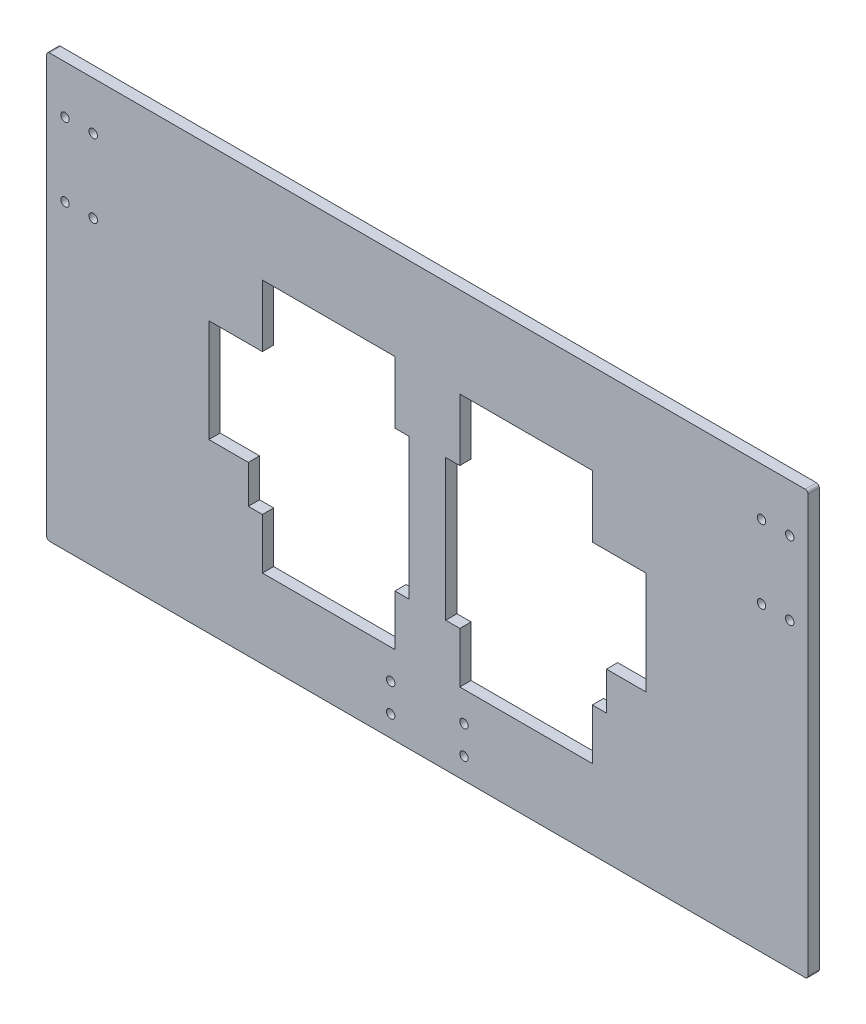
SolidWorks part; units mm, degrees
ref_plane "前视基准面" through (0, 0, 0) normal (0, 0, 1) x (1, 0, 0)
ref_plane "上视基准面" through (0, 0, 0) normal (0, 1, 0) x (1, 0, 0)
ref_plane "右视基准面" through (0, 0, 0) normal (1, 0, 0) x (0, 0, -1)
sketch "草图1" plane through (0, 0, 0) normal (0, 0, 1) x (1, 0, 0)
  line L1 (-135, -75) -> (135, -75)
  line L2 (-135, -75) -> (-135, 75)
  line L3 (-135, 75) -> (135, 75)
  line L4 (135, -75) -> (135, 75)
  line L5 (-135, -75) -> (135, 75) construction
  line L6 (-135, 75) -> (135, -75) construction
  point P0 (0, 0)
  dimension "D1" = 270
  dimension "D2" = 150
base flange "基体-法兰1" sketch "草图1" thickness 4 reverse thickness direction no parameters "D1"=10
fillet "圆角1" radius 1 4 edges at (135, -75, -2) (135, 75, -2) (-135, -75, -2) (-135, 75, -2)
sketch "草图2" plane through (0, 0, -4) normal (0, 0, -1) x (-1, 0, 0)
  line L0 (134, -75) -> (-134, -75) construction
  circle A0 centre (-13, -67.5) radius 1.5
  circle A1 centre (-13, -57.5) radius 1.5
  circle A2 centre (13, -57.5) radius 1.5
  circle A3 centre (13, -67.5) radius 1.5
  point P11 (0, 0)
  point P12 (0, 0)
  dimension "D1" = 3
  dimension "D2" = 3
  dimension "D3" = 3
  dimension "D4" = 3
  dimension "D5" = 13
  dimension "D6" = 13
  dimension "D7" = 13
  dimension "D8" = 13
  dimension "D9" = 7.5
  dimension "D10" = 7.5
  dimension "D11" = 10
  dimension "D12" = 10
extrude "切除-拉伸1" cut sketch "草图2" against normal blind 10 normal cut yes
sketch "草图3" plane through (0, 0, -4) normal (0, 0, -1) x (-1, 0, 0)
  line L0 (-135, -74) -> (-135, 74) construction
  line L1 (134, -75) -> (-134, -75) construction
  circle A0 centre (-128.5, 58) radius 1.5
  circle A1 centre (-128.5, 32) radius 1.5
  circle A2 centre (-118.5, 58) radius 1.5
  circle A3 centre (-118.5, 32) radius 1.5
  dimension "D7" = 3
  dimension "D8" = 3
  dimension "D9" = 3
  dimension "D10" = 3
  dimension "D1" = 6.5
  dimension "D2" = 6.5
  dimension "D3" = 10
  dimension "D4" = 10
  dimension "D5" = 26
  dimension "D6" = 26
  dimension "D11" = 107
extrude "切除-拉伸2" cut sketch "草图3" against normal blind 10 normal cut yes
mirror "镜向1" about plane through (0, 0, 0) normal (1, 0, 0) of "切除-拉伸2"
sketch "草图4" plane through (0, 0, -4) normal (0, 0, -1) x (-1, 0, 0)
  line L0 (134, -75) -> (-134, -75) construction
  line L1 (-58.5, -47) -> (-11.5, -47)
  line L2 (-58.5, -47) -> (-58.5, 43)
  line L3 (-58.5, 43) -> (-11.5, 43)
  line L4 (-11.5, -47) -> (-11.5, 43)
  line L5 (-58.5, -47) -> (-11.5, 43) construction
  line L6 (-58.5, 43) -> (-11.5, -47) construction
  point P0 (-35, -2)
  dimension "D1" = 47
  dimension "D2" = 90
  dimension "D3" = 35
  dimension "D4" = 28
extrude "切除-拉伸3" cut sketch "草图4" against normal blind 10 normal cut yes
sketch "草图5" plane through (0, 0, 0) normal (0, 0, 1) x (1, 0, 0)
  line L0 (11.5, 43) -> (58.5, 43) construction
  line L1 (6.5, -29) -> (63.5, -29)
  line L2 (6.5, -29) -> (6.5, 21)
  line L3 (6.5, 21) -> (63.5, 21)
  line L4 (63.5, -29) -> (63.5, 21)
  line L5 (6.5, -29) -> (63.5, 21) construction
  line L6 (6.5, 21) -> (63.5, -29) construction
  line L7 (58.5, -47) -> (11.5, -47) construction
  line L8 (11.5, -47) -> (11.5, 43) construction
  point P0 (35, -4)
  dimension "D1" = 57
  dimension "D2" = 22
  dimension "D3" = 18
  dimension "D4" = 5
extrude "切除-拉伸4" cut sketch "草图5" against normal blind 10 normal cut yes
sketch "草图6" plane through (0, 0, 0) normal (0, 0, 1) x (1, 0, 0)
  line L0 (58.5, -29) -> (63.5, -29) construction
  line L1 (63.5, 21) -> (77.5, 21)
  line L2 (63.5, 21) -> (63.5, -15.5)
  line L3 (63.5, -15.5) -> (77.5, -15.5)
  line L4 (77.5, 21) -> (77.5, -15.5)
  dimension "D1" = 14
  dimension "D2" = 13.5
extrude "切除-拉伸5" cut sketch "草图6" against normal blind 10 normal cut yes
mirror "镜向2" about plane through (0, 0, 0) normal (1, 0, 0) of "切除-拉伸3", "切除-拉伸4", "切除-拉伸5"
sketch "折弯-线1" [suppressed] plane through (0, 0, 0) normal (0, 1, 0) x (1, 0, 0)
sketch "边界框1" [suppressed] plane through (0, 0, 0) normal (0, 1, 0) x (1, 0, 0)
sheet metal parameters "钣金1" thickness 4 parameters "D1"=10
flat pattern "平板型式1" [suppressed]
sketch "折弯-线2" plane through (0, 0, 0) normal (0, 1, 0) x (1, 0, 0)
sketch3d "边界框2" [suppressed]
  line L0 (-135, -75, 0) -> (135, -75, 0) construction
  line L1 (-135, 75, 0) -> (135, 75, 0) construction
  line L2 (-135, -75, 0) -> (-135, 75, 0) construction
  line L3 (135, -75, 0) -> (135, 75, 0) construction
sheet metal parameters "钣金2" thickness 4 parameters "D1"=10
flat pattern "平板型式1"
sketch "折弯-线2" plane through (0, 0, 0) normal (0, 1, 0) x (1, 0, 0)
sketch3d "边界框2" [suppressed]
  line L0 (-135, -75, 0) -> (135, -75, 0) construction
  line L1 (-135, 75, 0) -> (135, 75, 0) construction
  line L2 (-135, -75, 0) -> (-135, 75, 0) construction
  line L3 (135, -75, 0) -> (135, 75, 0) construction
sheet metal parameters "钣金3" thickness 4 parameters "D1"=10
flat pattern "平板型式1"
sketch "折弯-线2" plane through (0, 0, 0) normal (0, 1, 0) x (1, 0, 0)
sketch3d "边界框2" [suppressed]
  line L0 (-135, -75, 0) -> (135, -75, 0) construction
  line L1 (-135, 75, 0) -> (135, 75, 0) construction
  line L2 (-135, -75, 0) -> (-135, 75, 0) construction
  line L3 (135, -75, 0) -> (135, 75, 0) construction
sheet metal parameters "钣金4" thickness 4 parameters "D1"=10
flat pattern "平板型式1"
sketch "折弯-线2" plane through (0, 0, 0) normal (0, 1, 0) x (1, 0, 0)
sketch3d "边界框2" [suppressed]
  line L0 (-135, -75, 0) -> (135, -75, 0) construction
  line L1 (-135, 75, 0) -> (135, 75, 0) construction
  line L2 (-135, -75, 0) -> (-135, 75, 0) construction
  line L3 (135, -75, 0) -> (135, 75, 0) construction
sheet metal parameters "钣金5" thickness 4 parameters "D1"=10
flat pattern "平板型式1"
sketch "折弯-线2" plane through (0, 0, 0) normal (0, 1, 0) x (1, 0, 0)
sketch3d "边界框2" [suppressed]
  line L0 (-135, -75, 0) -> (135, -75, 0) construction
  line L1 (-135, 75, 0) -> (135, 75, 0) construction
  line L2 (-135, -75, 0) -> (-135, 75, 0) construction
  line L3 (135, -75, 0) -> (135, 75, 0) construction
sheet metal parameters "钣金6" thickness 4 parameters "D1"=10
flat pattern "平板型式1"
sketch "折弯-线2" plane through (0, 0, 0) normal (0, 1, 0) x (1, 0, 0)
sketch3d "边界框2" [suppressed]
  line L0 (-135, -75, 0) -> (135, -75, 0) construction
  line L1 (-135, 75, 0) -> (135, 75, 0) construction
  line L2 (-135, -75, 0) -> (-135, 75, 0) construction
  line L3 (135, -75, 0) -> (135, 75, 0) construction
sheet metal parameters "钣金7" thickness 4 parameters "D1"=10
flat pattern "平板型式1"
sketch "折弯-线2" plane through (0, 0, 0) normal (0, 1, 0) x (1, 0, 0)
sketch3d "边界框2" [suppressed]
  line L0 (-135, -75, 0) -> (135, -75, 0) construction
  line L1 (-135, 75, 0) -> (135, 75, 0) construction
  line L2 (-135, -75, 0) -> (-135, 75, 0) construction
  line L3 (135, -75, 0) -> (135, 75, 0) construction
sheet metal parameters "钣金8" thickness 4 parameters "D1"=10
flat pattern "平板型式1"
sketch "折弯-线2" plane through (0, 0, 0) normal (0, 1, 0) x (1, 0, 0)
sketch3d "边界框2" [suppressed]
  line L0 (-135, -75, 0) -> (135, -75, 0) construction
  line L1 (-135, 75, 0) -> (135, 75, 0) construction
  line L2 (-135, -75, 0) -> (-135, 75, 0) construction
  line L3 (135, -75, 0) -> (135, 75, 0) construction
